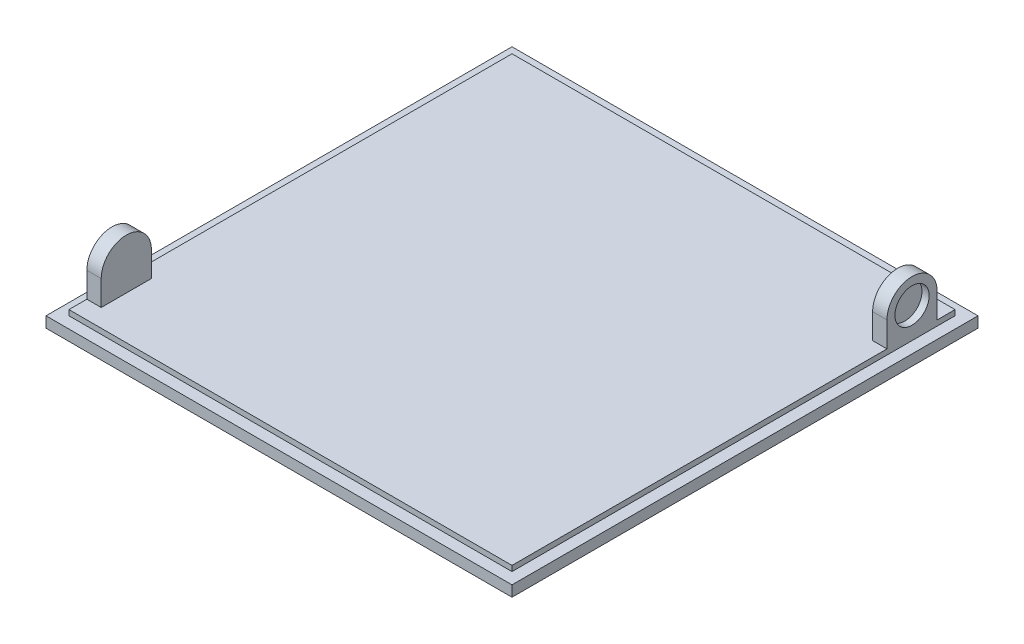
SolidWorks part; units mm, degrees
ref_plane "Front Plane" through (0, 0, 0) normal (0, 0, 1) x (1, 0, 0)
ref_plane "Top Plane" through (0, 0, 0) normal (0, 1, 0) x (1, 0, 0)
ref_plane "Right Plane" through (0, 0, 0) normal (1, 0, 0) x (0, 0, -1)
sketch "Sketch1" plane through (0, 0, 0) normal (0, 1, 0) x (1, 0, 0)
  line L1 (-65, 65) -> (65, 65)
  line L2 (-65, 65) -> (-65, -65)
  line L3 (-65, -65) -> (65, -65)
  line L4 (65, 65) -> (65, -65)
  line L5 (-65, 65) -> (65, -65) construction
  line L6 (-65, -65) -> (65, 65) construction
  point P0 (0, 0)
  dimension "D1" = 130
  dimension "D2" = 130
extrude "Boss-Extrude1" add sketch "Sketch1" along normal blind 3
sketch "Sketch2" plane through (0, 3, 0) normal (0, 1, 0) x (1, 0, 0)
  line L24 (61.8, -61.8) -> (61.8, 61.8)
  line L25 (-61.8, -61.8) -> (61.8, -61.8)
  line L26 (-61.8, 61.8) -> (-61.8, -61.8)
  line L27 (61.8, 61.8) -> (-61.8, 61.8)
  line L28 (61.8, -61.8) -> (61.8, 61.8)
  line L29 (-61.8, -61.8) -> (61.8, -61.8)
  line L30 (-61.8, 61.8) -> (-61.8, -61.8)
  line L31 (61.8, 61.8) -> (-61.8, 61.8)
  dimension "D1" = 3.2
extrude "Boss-Extrude2" add sketch "Sketch2" along normal blind 1.5
sketch "Sketch5" plane through (0, 4.5, 0) normal (0, 1, 0) x (1, 0, 0)
  line L0 (-61.8, 61.8) -> (-61.8, -61.8) construction
  line L1 (-61.8, -42.8) -> (-57.8, -42.8)
  line L2 (-61.8, -42.8) -> (-61.8, -56.8)
  line L3 (-61.8, -56.8) -> (-57.8, -56.8)
  line L4 (-57.8, -42.8) -> (-57.8, -56.8)
  line L5 (-61.8, 61.8) -> (-61.8, -61.8) construction
  line L6 (-61.8, -61.8) -> (61.8, -61.8) construction
  dimension "D1" = 4
  dimension "D2" = 14
  dimension "D3" = 5
extrude "Boss-Extrude3" add sketch "Sketch5" along normal blind 14
sketch "Sketch6" plane through (-61.8, 0, 0) normal (-1, 0, 0) x (0, 0, 1)
  line L0 (56.8, 18.5) -> (56.8, 4.5) construction
  line L1 (42.8, 18.5) -> (56.8, 18.5) construction
  circle A0 centre (49.8, 11.5) radius 4.775
  dimension "D1" = 9.55
  dimension "D2" = 7
  dimension "D3" = 7
extrude "Cut-Extrude3" cut sketch "Sketch6" against normal blind 2
fillet "Fillet1" 2 edges at (-59.8, 18.5, 56.8) (-59.8, 18.5, 42.8) type full round first side face at (-59.8, 11.5, 56.8) second side face at (-59.8, 11.5, 42.8) middle face at (-59.8, 18.5, 49.8)
ref_axis "Axis1" through (0, 19.425, 0) along (0, -1, 0)
pattern_circular "CirPattern2" count 2 every 180 about axis through (0, 19.425, 0) along (0, -1, 0) of "Boss-Extrude3", "Cut-Extrude3", "Fillet1"
